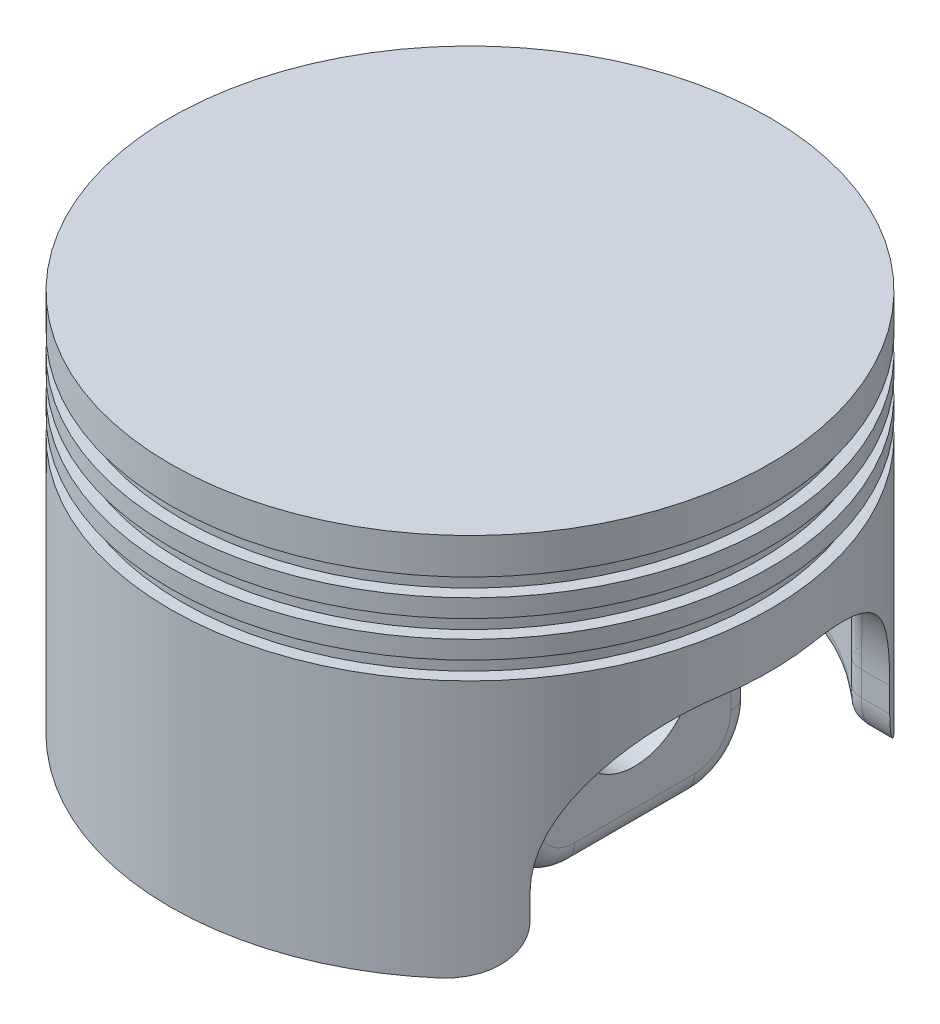
SolidWorks part; units mm, degrees
ref_plane "Front Plane" through (0, 0, 0) normal (0, 0, 1) x (1, 0, 0)
ref_plane "Top Plane" through (0, 0, 0) normal (0, 1, 0) x (1, 0, 0)
ref_plane "Right Plane" through (0, 0, 0) normal (1, 0, 0) x (0, 0, -1)
sketch "Sketch1" plane through (0, 0, 0) normal (1, 0, 0) x (0, 0, -1)
  line L0 (0, 0) -> (63.5, 0)
  line L1 (63.5, 0) -> (63.5, -81.28)
  line L2 (63.5, -81.28) -> (57.15, -81.28)
  line L3 (57.15, -81.28) -> (57.15, -19)
  line L4 (57.15, -19) -> (0, -19)
  line L5 (0, -19) -> (0, 0)
  dimension "D1" = 63.5
  dimension "D2" = 81.28
  dimension "D3" = 57.15
  dimension "D4" = 19
revolve "Revolve1" add sketch "Sketch1" angle 360 about L5
sketch "Sketch2" plane through (0, 0, 0) normal (0, 0, 1) x (1, 0, 0)
  line L0 (63.5, -7.62) -> (60.96, -7.62)
  line L1 (60.96, -7.62) -> (60.96, -11.43)
  line L2 (60.96, -11.43) -> (63.5, -11.43)
  line L3 (63.5, -11.43) -> (63.5, -7.62)
  line L4 (63.5, 0) -> (-63.5, 0) construction
  dimension "D1" = 2.54
  dimension "D2" = 3.81
  dimension "D3" = 7.62
  dimension "D4" = 63.5
ref_axis "Axis1" through (0, 4.064, 0) along (0, -1, 0)
revolve "Cut-Revolve1" cut sketch "Sketch2" angle 360 about axis through (0, 4.064, 0) along (0, -1, 0)
pattern_linear "LPattern1" count 3 spacing 7.62 along (0, -1, 0) of "Cut-Revolve1"
sketch "Sketch3" plane through (0, 0, 0) normal (1, 0, 0) x (0, 0, -1)
  line L0 (0, 4.064) -> (0, -85.344) construction
  line L1 (-38.1, -38.1) -> (38.1, -38.1)
  line L2 (-38.1, -38.1) -> (-38.1, -81.28)
  line L3 (-38.1, -81.28) -> (38.1, -81.28)
  line L4 (38.1, -38.1) -> (38.1, -81.28)
  line L5 (-38.1, -38.1) -> (38.1, -81.28) construction
  line L6 (-38.1, -81.28) -> (38.1, -38.1) construction
  line L7 (-57.15, -81.28) -> (57.15, -81.28) construction
  line L8 (63.5, 0) -> (-63.5, 0) construction
  point P0 (0, -59.69)
  dimension "D1" = 76.2
  dimension "D2" = 38.1
extrude "Cut-Extrude1" cut sketch "Sketch3" against normal mid plane 227
fillet "Fillet1" radius 28 4 edges at (-46.6985, -38.1, -38.1) (-46.6985, -38.1, 38.1) (46.6985, -38.1, -38.1) (46.6985, -38.1, 38.1)
sketch "Sketch4" plane through (0, -19, 0) normal (0, -1, 0) x (1, 0, 0)
  line L1 (-34.875, 25.4) -> (-15.875, 25.4)
  line L2 (-34.875, 25.4) -> (-34.875, -25.4)
  line L3 (-34.875, -25.4) -> (-15.875, -25.4)
  line L4 (-15.875, 25.4) -> (-15.875, -25.4)
  line L5 (-34.875, 25.4) -> (-15.875, -25.4) construction
  line L6 (-34.875, -25.4) -> (-15.875, 25.4) construction
  point P0 (-25.375, 0)
  dimension "D1" = 15.875
  dimension "D2" = 19
  dimension "D3" = 50.8
extrude "Boss-Extrude1" add sketch "Sketch4" along normal blind 63.5
mirror "Mirror1" about plane through (0, 0, 0) normal (1, 0, 0) of "Boss-Extrude1"
sketch "Sketch5" plane through (-34.875, 0, 0) normal (-1, 0, 0) x (0, 0, 1)
  line L0 (25.4, -82.5) -> (-25.4, -82.5) construction
  circle A0 centre (0, -57.1) radius 12.7
  dimension "D2" = 25.4
  dimension "D1" = 25.4
extrude "Cut-Extrude2" cut sketch "Sketch5" against normal blind 77.5
fillet "Fillet2" radius 12.7 4 edges at (-25.375, -82.5, -25.4) (-25.375, -82.5, 25.4) (25.375, -82.5, 25.4) (25.375, -82.5, -25.4)
fillet "Fillet3" radius 10 4 edges at (46.6985, -81.28, -38.1) (-46.6985, -81.28, -38.1) (-46.6985, -81.28, 38.1) (46.6985, -81.28, 38.1)
fillet "Fillet4" radius 5 20 edges at (15.875, -44.4, -25.4) (15.875, -78.7803, -21.6803) (15.875, -44.4, 25.4) (15.875, -78.7803, 21.6803) (34.875, -44.4, 25.4) (34.875, -78.7803, 21.6803) (34.875, -44.4, -25.4) (34.875, -78.7803, -21.6803) (-15.875, -44.4, -25.4) (-15.875, -78.7803, -21.6803) (-15.875, -44.4, 25.4) (-15.875, -78.7803, 21.6803) (-34.875, -44.4, 25.4) (-34.875, -78.7803, 21.6803) (-34.875, -44.4, -25.4) (-34.875, -78.7803, -21.6803) (15.875, -82.5, 0) (34.875, -82.5, 0) (-15.875, -82.5, 0) (-34.875, -82.5, 0)
fillet "Fillet5" radius 5 16 edges at (41.3657, -76.2692, 39.4335) (42.5971, -68.69, 38.1) (50.4318, -43.6881, 26.8841) (57.15, -38.1, 0) (46.055, -51.2516, -33.8387) (42.5971, -68.69, -38.1) (40.0022, -78.1316, -40.816) (0, -81.28, -57.15) (-41.3657, -76.2692, -39.4335) (-42.5971, -68.69, -38.1) (-50.4318, -43.6881, -26.8841) (-57.15, -38.1, 0) (-46.055, -51.2516, 33.8387) (-42.5971, -68.69, 38.1) (-40.0022, -78.1316, 40.816) (0, -81.28, 57.15)
